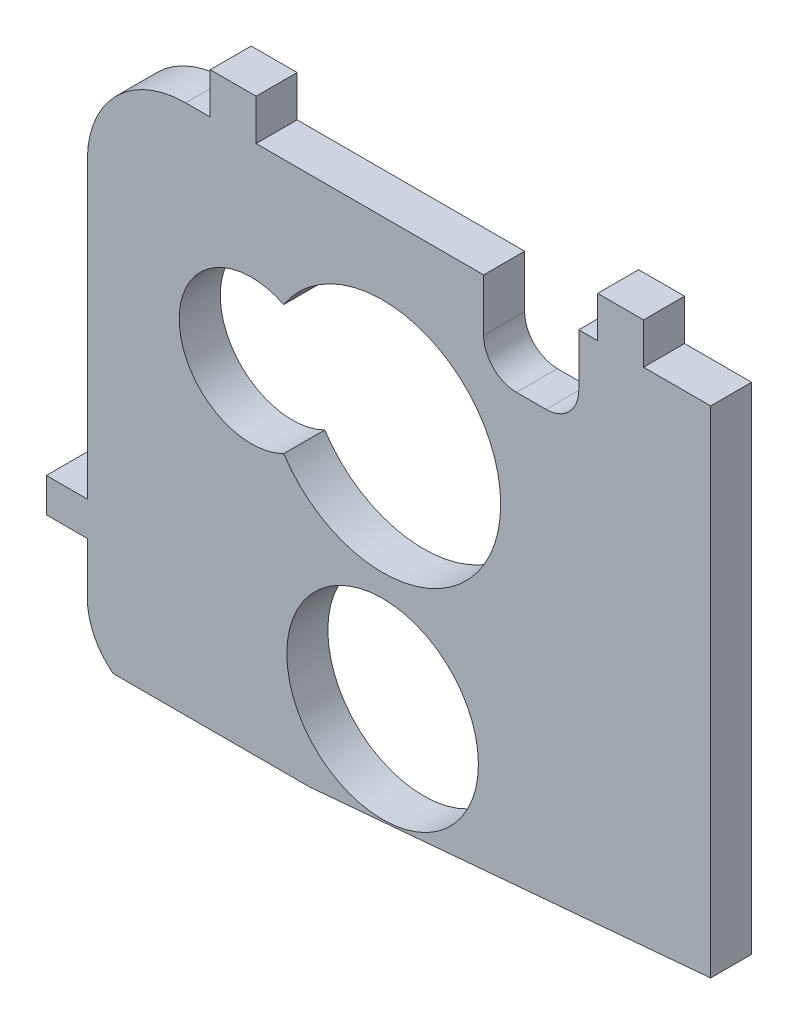
SolidWorks part; units mm, degrees
material "Balsa"
ref_plane "Front Plane" through (0, 0, 0) normal (0, 0, 1) x (1, 0, 0)
ref_plane "Top Plane" through (0, 0, 0) normal (0, 1, 0) x (1, 0, 0)
ref_plane "Right Plane" through (0, 0, 0) normal (1, 0, 0) x (0, 0, -1)
sketch "Sketch1" plane through (0, 0, 0) normal (0, 0, 1) x (1, 0, 0)
  line L0 (0, -1000.1535) -> (0, 48999.8465) construction
  line L1 (-2.8233, -4.0284) -> (-10.4313, -4.0284)
  line L2 (-1000, 0) -> (49000, 0) construction
  line L3 (12.7, 16.51) -> (-7.62, 16.51)
  line L4 (12.7, 16.51) -> (12.7, -2.6702)
  line L5 (8.3256, 18.0975) -> (10.1036, 18.0975)
  line L6 (12.7, -2.6702) -> (-8.6686, -4.5398)
  line L7 (-11.43, 12.7) -> (-11.43, -2.0094)
  line L8 (-6.6744, 16.51) -> (-4.8964, 16.51)
  line L9 (-6.6744, 16.51) -> (-6.6744, 18.0975)
  line L10 (-6.6744, 18.0975) -> (-4.8964, 18.0975)
  line L11 (-4.8964, 16.51) -> (-4.8964, 18.0975)
  line L12 (-11.43, 0) -> (-13.0175, 0)
  line L13 (-11.43, 0) -> (-11.43, 1.3208)
  line L14 (-11.43, 1.3208) -> (-13.0175, 1.3208)
  line L15 (-13.0175, 0) -> (-13.0175, 1.3208)
  line L16 (10.1036, 16.51) -> (10.1036, 18.0975)
  line L17 (8.3256, 16.51) -> (10.1036, 16.51)
  line L18 (8.3256, 16.51) -> (8.3256, 18.0975)
  circle A0 centre (0, 0) radius 3.7084
  arc A1 (-3.829, 6.6457) -> (-3.829, 11.6423) centre (0, 9.144) ccw
  arc A2 (-3.829, 11.6423) -> (-3.829, 6.6457) centre (-5.08, 9.144) ccw
  arc A3 (-7.62, 16.51) -> (-11.43, 12.7) centre (-7.62, 12.7) ccw
  arc A4 (-8.6686, -4.5398) -> (-11.43, -2.0094) centre (-8.89, -2.0094) cw
  dimension "D1" = 7.4168
  dimension "D4" = 7.366
  dimension "D3" = 9.144
  dimension "D5" = 5.588
  dimension "D9" = 3.81
  dimension "D10" = 11.43
  dimension "D14" = 1.5875
  dimension "D12" = 2.54
  dimension "D2" = 12.7
  dimension "D6" = 9.144
  dimension "D7" = 5.08
  dimension "D8" = 6.35
  dimension "D11" = 5
  dimension "D13" = 3.767
  dimension "D15" = 1.778
  dimension "D16" = 1.5875
  dimension "D17" = 1.3208
  dimension "D18" = 1.778
  dimension "D19" = 1.5875
extrude "Boss-Extrude1" add sketch "Sketch1" along normal blind 1.5875 contours A4 L1 L6 L4 L3 A3 L7 A2 A1 A0 | L3 L9 | L18 L3 L16 L5 | L15 L14 L13 L12 region at (-6.6273, -3.7115, 0) region at (9.2146, 17.3037, 0) region at (-5.7854, 17.3037, 0)
sketch "Sketch3" plane through (0, 0, 1.5875) normal (0, 0, 1) x (1, 0, 0)
  line L0 (6.8073, 16.51) -> (6.8073, 18.0975) construction
  line L1 (6.8073, 16.51) -> (6.8073, 18.0975) construction
  line L2 (4.6991, 18.0975) -> (4.6991, 16.51) construction
  line L3 (4.6991, 18.0975) -> (4.6991, 16.51) construction
  line L4 (8.3256, 16.51) -> (-4.8964, 16.51) construction
  line L5 (7.5947, 16.51) -> (3.9117, 16.51)
  line L6 (7.5947, 16.51) -> (7.5947, 13.208)
  line L7 (7.5947, 13.208) -> (3.9117, 13.208)
  line L8 (3.9117, 16.51) -> (3.9117, 13.208)
  line L9 (6.8073, 17.6426) -> (7.5947, 17.6426) construction
  line L10 (4.6991, 17.6426) -> (3.9117, 17.6426) construction
  line L11 (3.9117, 17.6426) -> (3.9117, 16.51) construction
  line L12 (7.5947, 17.6426) -> (7.5947, 16.51) construction
  dimension "D1" = 3.302
  dimension "D2" = 3.683
extrude "Cut-Extrude1" cut sketch "Sketch3" against normal through all
fillet "Fillet1" radius 1.27 2 edges at (7.5947, 13.208, 0.7937) (3.9117, 13.208, 0.7937)
